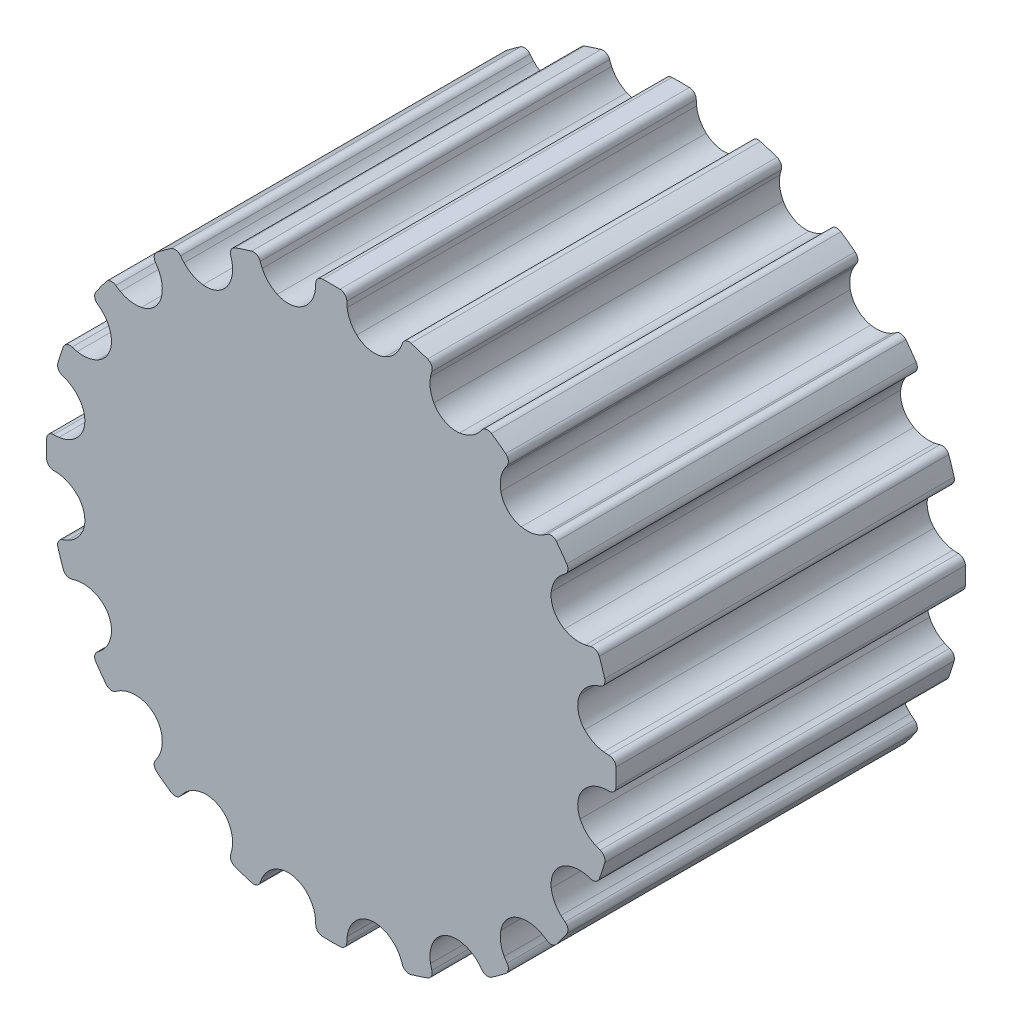
SolidWorks part; units mm, degrees
ref_plane "Front Plane" through (0, 0, 0) normal (0, 0, 1) x (1, 0, 0)
ref_plane "Top Plane" through (0, 0, 0) normal (0, 1, 0) x (1, 0, 0)
ref_plane "Right Plane" through (0, 0, 0) normal (1, 0, 0) x (0, 0, -1)
sketch "Sketch1" plane through (0, 0, 0) normal (0, 0, 1) x (1, 0, 0)
  line L0 (0, 0) -> (0, 6.3662) construction
  line L1 (0, 0) -> (0.9959, 6.2878) construction
  line L2 (0, 0) -> (1.3887, 6.2129) construction
  circle A0 centre (0, 0) radius 6.3662 construction
  circle A1 centre (0, 0) radius 5.3622 construction
  circle A2 centre (0, 0) radius 6.1122 construction
  arc A3 (0.8388, 5.2962) -> (0.5472, 5.4384) centre (0.9257, 5.8443) cw
  arc A4 (0.3406, 5.8443) -> (0.3333, 5.9601) centre (1.3333, 5.965) cw
  circle A5 centre (0, 0) radius 5.9622 construction
  arc A6 (-0.188, 6.1093) -> (0.188, 6.1093) centre (0, 0) cw
  arc A7 (0.188, 6.1093) -> (0.3333, 5.9601) centre (0.1833, 5.9594) cw
  arc A8 (0.3406, 5.8443) -> (0.5472, 5.4384) centre (1.0004, 5.9245) ccw
  arc A9 (-0.8388, 5.2962) -> (-0.5472, 5.4384) centre (-0.9257, 5.8443) ccw
  arc A10 (-0.3406, 5.8443) -> (-0.5472, 5.4384) centre (-1.0004, 5.9245) cw
  arc A11 (-0.3406, 5.8443) -> (-0.3333, 5.9601) centre (-1.3333, 5.965) ccw
  arc A12 (-0.188, 6.1093) -> (-0.3333, 5.9601) centre (-0.1833, 5.9594) ccw
  arc A13 (-0.8388, 5.2962) -> (0.8388, 5.2962) centre (0, 0) cw
  dimension "D1" = 12.7324
  dimension "D6" = 0.555
  dimension "D7" = 1
  dimension "D9" = 0.15
  dimension "D2" = 9
  dimension "D3" = 3.6
  dimension "D4" = 1.004
  dimension "D5" = 0.75
  dimension "D8" = 0.15
extrude "Boss-Extrude1" add sketch "Sketch1" along normal blind 7.5
ref_axis "Axis1" through (0, 0, -0.375) along (0, 0, 1)
pattern_circular "CirPattern1" count 20 over 360 about axis through (0, 0, -0.375) along (0, 0, 1) of "Boss-Extrude1"
sketch "Sketch2" plane through (0, 0, 0) normal (0, 0, -1) x (-1, 0, 0)
  circle A0 centre (0, 0) radius 5.3622
  arc A1 (0.8388, 5.2962) -> (-0.8388, 5.2962) centre (0, 0) ccw construction
extrude "Boss-Extrude2" add sketch "Sketch2" against normal up to surface (7.5 mm away)
equation "\"NumTeeth\"= 20'The number of teeth that the pulley has"
equation "\"ToothPitch\"= 2.00mm'Distance between 2 teeth"
equation "\"PulleyDia\"= \"NumTeeth\" * \"ToothPitch\" / PI"
equation "\"ToothAng\"= ( 360deg / \"NumTeeth\" ) * 1deg"
equation "\"TransOffsetAngle\"= \"ToothAng\" * .2deg"
equation "\"ShoulderRad\"= 0.15mm"
equation "\"RootRad\"= 0.555mm"
equation "\"TransRad\"= 1mm"
equation "\"ToothHeight\"= 0.75mm"
equation "\"PLD\"= 0.254mm"
equation "\"D1@CirPattern1\"=\"NumTeeth\""
equation "\"D1@Sketch1\"=\"PulleyDia\""
equation "\"D7@Sketch1\"=\"TransRad\""
equation "\"D9@Sketch1\"=\"ShoulderRad\""
equation "\"D6@Sketch1\"=\"RootRad\""
equation "\"D3@Sketch1\"=\"TransOffsetAngle\""
equation "\"D5@Sketch1\"=\"ToothHeight\""
equation "\"D2@Sketch1\"=\"ToothAng\"/2"
equation "\"D4@Sketch1\"=\"PLD\"+\"ToothHeight\""
equation "\"D8@Sketch1\"=\"ShoulderRad\""
